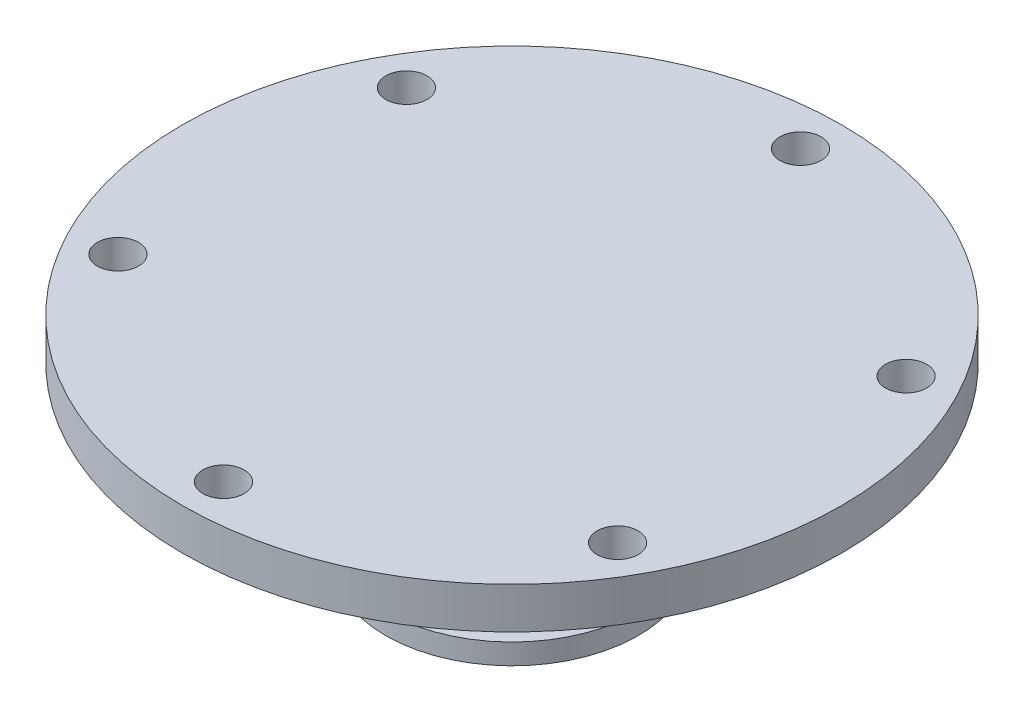
SolidWorks part; units mm, degrees
ref_plane "Front Plane" through (0, 0, 0) normal (0, 0, 1) x (1, 0, 0)
ref_plane "Top Plane" through (0, 0, 0) normal (0, 1, 0) x (1, 0, 0)
ref_plane "Right Plane" through (0, 0, 0) normal (1, 0, 0) x (0, 0, -1)
ref_axis "Centerline" through (0, 21.4963, 0) along (0, -1, 0)
sketch "Sketch1" plane through (0, 0, 0) normal (0, 1, 0) x (1, 0, 0)
  circle A0 centre (0, 0) radius 20.32
  dimension "D1" = 40.64
extrude "Cylinder" add sketch "Sketch1" along normal blind 14.478
sketch "Sketch2" plane through (0, 0, 0) normal (0, 0, 1) x (1, 0, 0)
  line L0 (0, 20.1077) -> (0, -7.6632) construction
  line L1 (20.32, 0) -> (12.7, 0)
  line L2 (20.32, 0) -> (20.32, 11.938)
  line L3 (20.32, 11.938) -> (12.7, 11.938)
  line L4 (12.7, 0) -> (12.7, 11.938)
  line L5 (20.32, 14.478) -> (-20.32, 14.478) construction
  dimension "D1" = 12.7
  dimension "D2" = 2.54
revolve "Mid O Ring Wings" cut sketch "Sketch2" angle 360 about axis through (0, 21.4963, 0) along (0, -1, 0)
sketch "Sketch3" plane through (0, 0, 0) normal (0, 0, 1) x (1, 0, 0)
  line L0 (12.7, 0) -> (12.7, 11.938) construction
  line L1 (12.7, 10.668) -> (10.414, 10.668)
  line L2 (12.7, 10.668) -> (12.7, 7.874)
  line L3 (12.7, 7.874) -> (10.414, 7.874)
  line L4 (10.414, 10.668) -> (10.414, 7.874)
  line L5 (-12.7, 11.938) -> (12.7, 11.938) construction
  dimension "D1" = 1.27
  dimension "D2" = 2.286
  dimension "D3" = 2.794
revolve "Mid O Ring Cut" cut sketch "Sketch3" angle 360 about axis through (0, 21.4963, 0) along (0, -1, 0)
sketch "Sketch4" plane through (0, 0, 0) normal (0, 0, 1) x (1, 0, 0)
  line L0 (12.7, 7.874) -> (-12.7, 7.874) construction
  line L2 (12.7, 0) -> (12.7, 6.604)
  line L3 (12.7, 6.604) -> (7.7902, 6.604)
  line L5 (0, 20.9905) -> (0, -6.9276) construction
  line L6 (7.7902, 0) -> (0, 0) construction
  line L7 (7.7902, 6.604) -> (7.7902, 0)
  line L8 (7.7902, 0) -> (12.7, 0)
  dimension "D1" = 1.27
  dimension "D2" = 7.7902
revolve "Bottom O Ring Wings" cut sketch "Sketch4" angle 360 about axis through (0, 21.4963, 0) along (0, -1, 0)
sketch "Sketch5" plane through (0, 0, 0) normal (0, 0, 1) x (1, 0, 0)
  line L0 (7.7902, 0) -> (7.7902, 6.604) construction
  line L1 (7.7902, 5.334) -> (5.5042, 5.334)
  line L2 (7.7902, 5.334) -> (7.7902, 2.54)
  line L3 (7.7902, 2.54) -> (5.5042, 2.54)
  line L4 (5.5042, 5.334) -> (5.5042, 2.54)
  line L5 (-7.7902, 6.604) -> (7.7902, 6.604) construction
  dimension "D1" = 1.27
  dimension "D2" = 2.794
  dimension "D3" = 2.286
revolve "Bottom O Ring Cut" cut sketch "Sketch5" angle 360 about axis through (0, 21.4963, 0) along (0, -1, 0)
chamfer "Bottom Chamfer" distance 7.7902 distance2 1.27 1 edges at (0, 0, 7.7902) first distance on face at (0, 0, 7.7902)
sketch "Sketch6" plane through (0, 14.478, 0) normal (0, 1, 0) x (1, 0, 0)
  circle A0 centre (0, 17.78) radius 1.27
  circle A1 centre (0, 0) radius 20.32 construction
  dimension "D1" = 2.54
  dimension "D2" = 17.78
extrude "Mounting Hole" cut sketch "Sketch6" against normal up to next
pattern_circular "Mounting Hole Pattern" count 6 over 360 about axis through (0, 14.478, 0) along (0, 1, 0) of "Mounting Hole"
